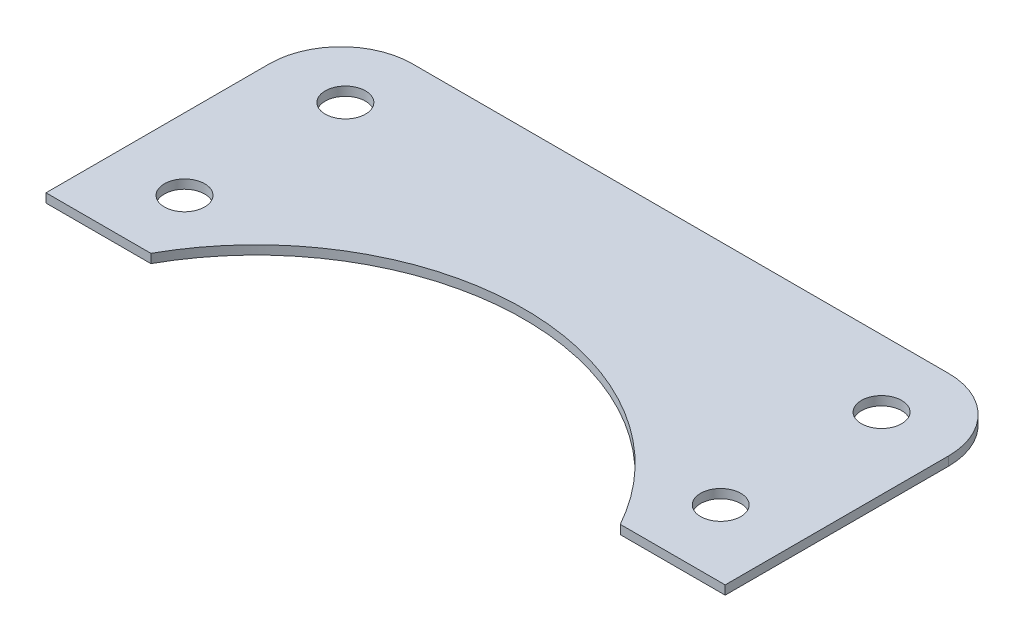
SolidWorks part; units mm, degrees
material "ABS PC"
ref_plane "Front Plane" through (0, 0, 0) normal (0, 0, 1) x (1, 0, 0)
ref_plane "Top Plane" through (0, 0, 0) normal (0, 1, 0) x (1, 0, 0)
ref_plane "Right Plane" through (0, 0, 0) normal (1, 0, 0) x (0, 0, -1)
sketch "Sketch1" plane through (0, 0, 0) normal (0, 1, 0) x (1, 0, 0)
  line L0 (0, 104.775) -> (0, -104.775) construction
  line L1 (-241.3, 104.775) -> (241.3, 104.775)
  line L2 (-241.3, 104.775) -> (-241.3, -104.775)
  line L3 (-241.3, -104.775) -> (241.3, -104.775)
  line L4 (241.3, 104.775) -> (241.3, -104.775)
  line L5 (-241.3, 104.775) -> (241.3, -104.775) construction
  line L6 (-241.3, -104.775) -> (241.3, 104.775) construction
  circle A0 centre (-190.5, 57.15) radius 14.3256
  circle A1 centre (-190.5, -57.15) radius 14.3129
  circle A2 centre (190.5, -57.15) radius 14.3129
  circle A3 centre (190.5, 57.15) radius 14.3256
  circle A4 centre (0, -196.85) radius 190.5
  point P0 (0, 0)
  point P18 (0, -205.6247)
  point P19 (0, -203.2)
  dimension "D3" = 28.6512
  dimension "D8" = 28.6258
  dimension "D9" = 381
  dimension "D1" = 209.55
  dimension "D2" = 482.6
  dimension "D4" = 190.5
  dimension "D5" = 57.15
  dimension "D6" = 57.15
  dimension "D7" = 190.5
  dimension "D10" = 196.85
extrude "Boss-Extrude1" add sketch "Sketch1" along normal blind 6.35 contours A4 L3 L4 L1 L2 A2 A1 A0 A3 region at (0, 0, -19.9787)
fillet "Fillet1" radius 50.8 2 edges at (241.3, 3.175, -104.775) (-241.3, 3.175, -104.775)
